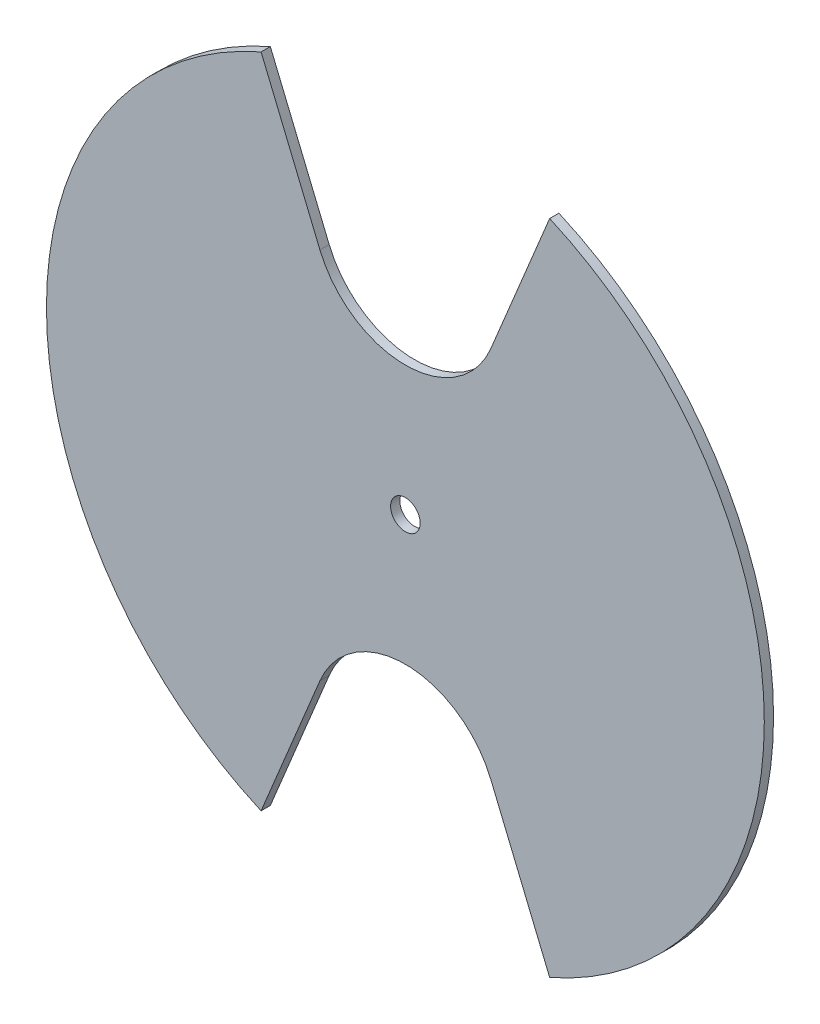
SolidWorks part; units mm, degrees
ref_plane "Front Plane" through (0, 0, 0) normal (0, 0, 1) x (1, 0, 0)
ref_plane "Top Plane" through (0, 0, 0) normal (0, 1, 0) x (1, 0, 0)
ref_plane "Right Plane" through (0, 0, 0) normal (1, 0, 0) x (0, 0, -1)
sketch "Esquisse1" plane through (0, 0, 0) normal (0, 0, 1) x (1, 0, 0)
  circle A0 centre (0, 0) radius 97
  circle A1 centre (0, 0) radius 4
  dimension "D1" = 194
  dimension "D2" = 8
extrude "Boss.-Extru.1" add sketch "Esquisse1" along normal blind 2.5
sketch "Esquisse2" plane through (0, 0, 2.5) normal (0, 0, 1) x (1, 0, 0)
  line L0 (-23.097, 50.4329) -> (-38.9959, 88.8162)
  line L1 (23.097, 50.4329) -> (38.9959, 88.8162)
  arc A0 (-23.097, 50.4329) -> (23.097, 50.4329) centre (0, 60) ccw
  circle A1 centre (0, 0) radius 97 construction
  point P3 (0, 0)
  point P8 (0, 0)
  dimension "D2" = 25
  dimension "D1" = 45
  dimension "D3" = 60
extrude "Enlèv. mat.-Extru.1" cut sketch "Esquisse2" against normal through all and the other way through all
mirror "Symétrie1" about plane through (0, 0, 0) normal (0, 1, 0) of "Enlèv. mat.-Extru.1"
